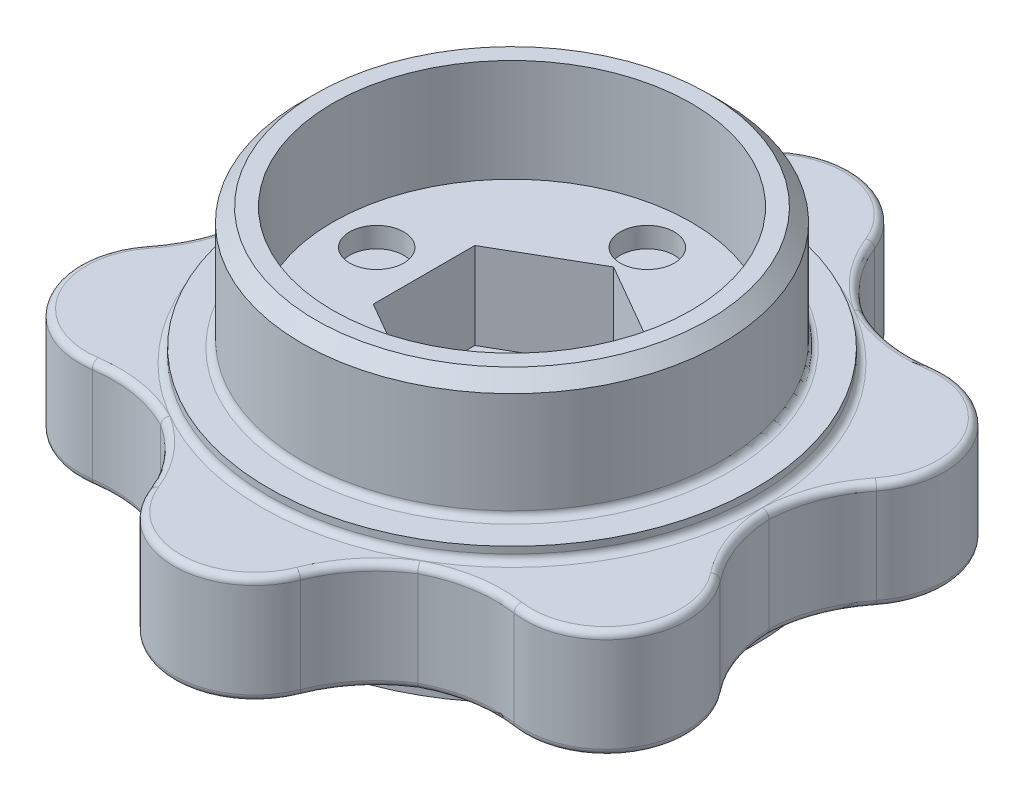
SolidWorks part; units mm, degrees
ref_plane "Front Plane" through (0, 0, 0) normal (0, 0, 1) x (1, 0, 0)
ref_plane "Top Plane" through (0, 0, 0) normal (0, 1, 0) x (1, 0, 0)
ref_plane "Right Plane" through (0, 0, 0) normal (1, 0, 0) x (0, 0, -1)
sketch "Sketch1" plane through (0, 0, 0) normal (0, 1, 0) x (1, 0, 0)
  circle A0 centre (0, 0) radius 19
  circle A1 centre (0, 19) radius 6
  circle A2 centre (16.4545, 9.5) radius 6
  circle A3 centre (16.4545, -9.5) radius 6
  circle A4 centre (0, -19) radius 6
  circle A5 centre (-16.4545, -9.5) radius 6
  circle A6 centre (-16.4545, 9.5) radius 6
  point P11 (0, 0)
  dimension "D1" = 38
  dimension "D3" = 12
  dimension "D2" = 6
extrude "Boss-Extrude1" add sketch "Sketch1" along normal blind 8 contours A6 A0 A5 A4 A3 A2 A1 | A0 A6 | A0 A6 | A0 A1 | A0 A1 | A0 A2 | A0 A2 | A0 A3 | A0 A3 | A0 A4 | A0 A4 | A0 A5 | A0 A5 | A6 region at (0, 0, 0) region at (14.1081, 0, -8.1453) region at (18.5054, 0, -10.6841) region at (18.5054, 0, 10.6841) region at (14.1081, 0, 8.1453) region at (0, 0, -16.2906) region at (0, 0, -21.3682) region at (0, 0, 21.3682) region at (0, 0, 16.2906) region at (-14.1081, 0, -8.1453) region at (-18.5054, 0, -10.6841) region at (-18.5054, 0, 10.6841) region at (-14.1081, 0, 8.1453)
fillet "Fillet2" radius 10 12 edges at (5.9247, 4, 18.0526) (12.6717, 4, 14.1573) (18.5964, 4, 3.8953) (18.5964, 4, -3.8953) (12.6717, 4, -14.1573) (5.9247, 4, -18.0526) (-5.9247, 4, -18.0526) (-12.6717, 4, -14.1573) (-18.5964, 4, -3.8953) (-18.5964, 4, 3.8953) (-5.9247, 4, 18.0526) (-12.6717, 4, 14.1573)
ref_plane "Plane1" through (0, 4, 0) normal (0, -1, 0) x (-1, 0, 0)
sketch "Sketch2" plane through (0, 4, 0) normal (0, -1, 0) x (-1, 0, 0)
  circle A0 centre (0, 0) radius 18
  dimension "D1" = 36
extrude "Boss-Extrude2" add sketch "Sketch2" along normal blind 5 and the other way blind 5
sketch "Sketch3" plane through (0, 4, 0) normal (0, -1, 0) x (-1, 0, 0)
  circle A0 centre (0, 0) radius 15.5
  dimension "D1" = 31
extrude "Boss-Extrude3" add sketch "Sketch3" along normal blind 5.5 and the other way blind 14
sketch "Sketch4" plane through (0, 4, 0) normal (0, -1, 0) x (-1, 0, 0)
  line L1 (0, 7.5056) -> (-6.5, 3.7528)
  line L2 (-6.5, 3.7528) -> (-6.5, -3.7528)
  line L3 (-6.5, -3.7528) -> (0, -7.5056)
  line L4 (0, -7.5056) -> (6.5, -3.7528)
  line L5 (6.5, -3.7528) -> (6.5, 3.7528)
  line L6 (6.5, 3.7528) -> (0, 7.5056)
  circle A0 centre (0, 0) radius 6.5 construction
  dimension "D1" = 13
extrude "Cut-Extrude1" cut sketch "Sketch4" against normal through all
sketch "Sketch5" plane through (0, 4, 0) normal (0, 1, 0) x (1, 0, 0)
  circle A0 centre (0, 0) radius 4.5
  dimension "D1" = 9
extrude "Cut-Extrude2" cut sketch "Sketch5" against normal through all
sketch "Sketch6" plane through (0, -1.5, 0) normal (0, -1, 0) x (1, 0, 0)
  circle A0 centre (0, 0) radius 13.25
  dimension "D1" = 26.5
extrude "Cut-Extrude3" cut sketch "Sketch6" against normal blind 3
ref_plane "Plane2" through (0, 10.4, 0) normal (0, 1, 0) x (1, 0, 0)
sketch "Sketch9" plane through (0, 10.4, 0) normal (0, 1, 0) x (1, 0, 0)
  circle A0 centre (0, 0) radius 13.25
  dimension "D1" = 26.5
extrude "Cut-Extrude5" cut sketch "Sketch9" along normal through all
sketch "Sketch10" plane through (0, 10.4, 0) normal (0, 1, 0) x (1, 0, 0)
  circle A0 centre (0, 0) radius 10 construction
  circle A1 centre (0, 10) radius 2
  circle A2 centre (0, -10) radius 2
  circle A3 centre (-10, 0) radius 2
  circle A4 centre (10, 0) radius 2
  dimension "D1" = 4
  dimension "D2" = 20
extrude "Cut-Extrude6" cut sketch "Sketch10" against normal blind 1.5
chamfer "Chamfer1" distance 1 angle 45 1 edges at (0, 18, -15.5)
fillet "Fillet4" radius 0.5 18 edges at (12.4606, 8, 15.4681) (19.6261, 8, 3.0572) (21.6506, 8, 12.5) (0, 8, -25) (7.1655, 8, -18.5253) (12.4606, 8, -15.4681) (21.6506, 8, -12.5) (19.6261, 8, -3.0572) (7.1655, 8, 18.5253) (0, 8, 25) (-7.1655, 8, 18.5253) (-12.4606, 8, 15.4681) (-21.6506, 8, 12.5) (-19.6261, 8, 3.0572) (-19.6261, 8, -3.0572) (-21.6506, 8, -12.5) (-12.4606, 8, -15.4681) (-7.1655, 8, -18.5253)
fillet "Fillet5" radius 0.5 19 edges at (-12.4606, 0, 15.4681) (-7.1655, 0, 18.5253) (0, 0, 25) (7.1655, 0, 18.5253) (12.4606, 0, 15.4681) (21.6506, 0, 12.5) (19.6261, 0, 3.0572) (19.6261, 0, -3.0572) (21.6506, 0, -12.5) (12.4606, 0, -15.4681) (7.1655, 0, -18.5253) (0, 0, -25) (-7.1655, 0, -18.5253) (-12.4606, 0, -15.4681) (-21.6506, 0, -12.5) (-19.6261, 0, -3.0572) (-19.6261, 0, 3.0572) (-21.6506, 0, 12.5) (0, 0, 18)
fillet "Fillet6" radius 0.5 2 edges at (0, 8, 18) (0, 9, -15.5)
